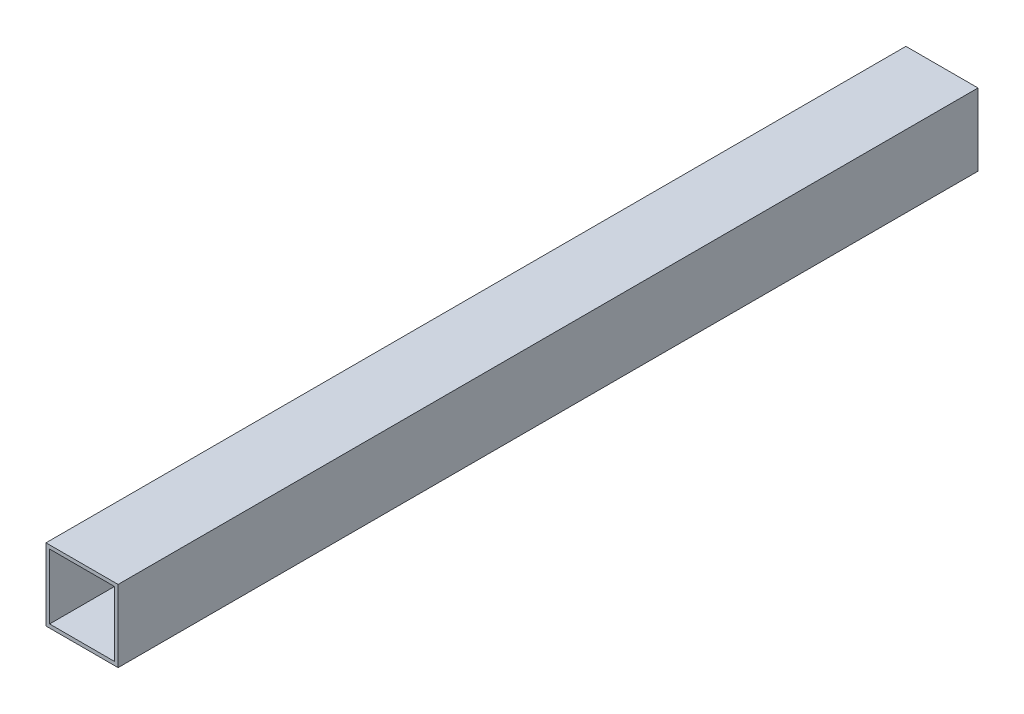
SolidWorks part; units mm, degrees
ref_plane "前视基准面" through (0, 0, 0) normal (0, 0, 1) x (1, 0, 0)
ref_plane "上视基准面" through (0, 0, 0) normal (0, 1, 0) x (1, 0, 0)
ref_plane "右视基准面" through (0, 0, 0) normal (1, 0, 0) x (0, 0, -1)
other "Configuration Table"
sketch "草图1" plane through (0, 0, 0) normal (0, 0, 1) x (1, 0, 0)
  line L0 (-9, 9) -> (9, 9)
  line L1 (-10, 10) -> (10, 10)
  line L2 (-10, 10) -> (-10, -10)
  line L3 (-10, -10) -> (10, -10)
  line L4 (10, 10) -> (10, -10)
  line L5 (-10, 10) -> (10, -10) construction
  line L6 (-10, -10) -> (10, 10) construction
  line L7 (9, 9) -> (9, -9)
  line L8 (-9, -9) -> (9, -9)
  line L9 (-9, 9) -> (-9, -9)
  point P0 (0, 0)
  dimension "D1" = 20
  dimension "D2" = 20
  dimension "D3" = 1
extrude "凸台-拉伸1" add sketch "草图1" along normal blind 238.56
